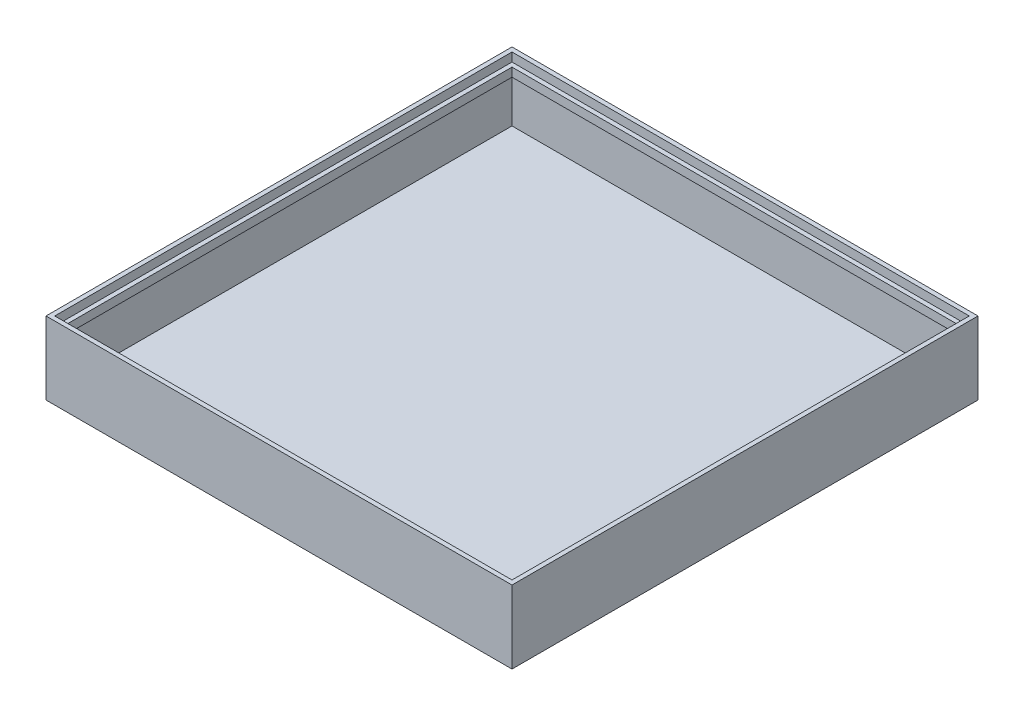
SolidWorks part; units mm, degrees
ref_plane "Front Plane" through (0, 0, 0) normal (0, 0, 1) x (1, 0, 0)
ref_plane "Top Plane" through (0, 0, 0) normal (0, 1, 0) x (1, 0, 0)
ref_plane "Right Plane" through (0, 0, 0) normal (1, 0, 0) x (0, 0, -1)
sketch "Sketch2" plane through (0, 0, 0) normal (0, 1, 0) x (1, 0, 0)
  line L1 (-80, -80) -> (80, -80)
  line L2 (-80, -80) -> (-80, 80)
  line L3 (-80, 80) -> (80, 80)
  line L4 (80, -80) -> (80, 80)
  line L5 (-80, -80) -> (80, 80) construction
  line L6 (-80, 80) -> (80, -80) construction
  point P0 (0, 0)
  dimension "D1" = 160
  dimension "D2" = 160
extrude "Outer Block" add sketch "Sketch2" along normal blind 25
sketch "Sketch12" plane through (0, 25, 0) normal (0, 1, 0) x (1, 0, 0)
  line L1 (78.5, -78.5) -> (-78.5, -78.5)
  line L2 (78.5, -78.5) -> (78.5, 78.5)
  line L3 (78.5, 78.5) -> (-78.5, 78.5)
  line L4 (-78.5, -78.5) -> (-78.5, 78.5)
  line L5 (78.5, -78.5) -> (-78.5, 78.5) construction
  line L6 (78.5, 78.5) -> (-78.5, -78.5) construction
  point P0 (0, 0)
  dimension "D1" = 157
  dimension "D2" = 157
extrude "Cut-Extrude1" cut sketch "Sketch12" against normal blind 3
sketch "Sketch13" plane through (0, 0, 0) normal (0, -1, 0) x (1, 0, 0)
  line L1 (-78.5, -78.5) -> (78.5, -78.5)
  line L2 (-78.5, -78.5) -> (-78.5, 78.5)
  line L3 (-78.5, 78.5) -> (78.5, 78.5)
  line L4 (78.5, -78.5) -> (78.5, 78.5)
  line L5 (-78.5, -78.5) -> (78.5, 78.5) construction
  line L6 (-78.5, 78.5) -> (78.5, -78.5) construction
  point P0 (0, 0)
  dimension "D1" = 157
  dimension "D2" = 157
ref_plane "Plane2" through (0, 3, 0) normal (0, -1, 0) x (-1, 0, 0)
sketch "Sketch14" plane through (0, 3, 0) normal (0, -1, 0) x (-1, 0, 0)
  line L1 (-78.5, -78.5) -> (78.5, -78.5)
  line L2 (-78.5, -78.5) -> (-78.5, 78.5)
  line L3 (-78.5, 78.5) -> (78.5, 78.5)
  line L4 (78.5, -78.5) -> (78.5, 78.5)
  line L5 (-78.5, -78.5) -> (78.5, 78.5) construction
  line L6 (-78.5, 78.5) -> (78.5, -78.5) construction
  point P0 (0, 0)
  dimension "D1" = 157
  dimension "D2" = 157
extrude "Cut-Extrude4" cut sketch "Sketch14" against normal blind 16
sketch "Sketch15" plane through (0, 22, 0) normal (0, 1, 0) x (1, 0, 0)
  line L1 (-77, -77) -> (77, -77)
  line L2 (-77, -77) -> (-77, 77)
  line L3 (-77, 77) -> (77, 77)
  line L4 (77, -77) -> (77, 77)
  line L5 (-77, -77) -> (77, 77) construction
  line L6 (-77, 77) -> (77, -77) construction
  point P0 (0, 0)
  dimension "D1" = 154
  dimension "D2" = 154
extrude "Cut-Extrude6" cut sketch "Sketch15" against normal blind 5
